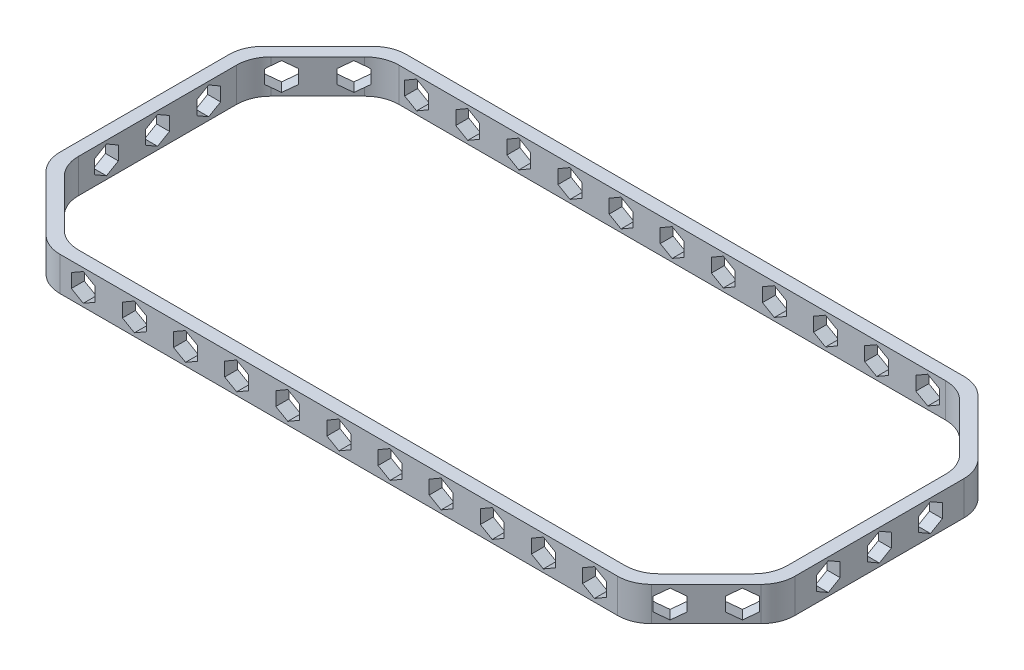
SolidWorks part; units mm, degrees
ref_plane "前视基准面" through (0, 0, 0) normal (0, 0, 1) x (1, 0, 0)
ref_plane "上视基准面" through (0, 0, 0) normal (0, 1, 0) x (1, 0, 0)
ref_plane "右视基准面" through (0, 0, 0) normal (1, 0, 0) x (0, 0, -1)
other "Configuration Table"
sketch "草图1" plane through (0, 0, 0) normal (0, 1, 0) x (1, 0, 0)
  line L0 (85.4765, 52.2785) -> (-86.5723, 52.2785)
  line L1 (-86.5723, 52.2785) -> (-108.5479, 30.3029)
  line L2 (-108.5479, 30.3029) -> (-108.5479, -27.7459)
  line L3 (-108.5479, -27.7459) -> (-86.5723, -49.7215)
  line L4 (-86.5723, -49.7215) -> (85.4765, -49.7215)
  line L5 (85.4765, -49.7215) -> (107.4521, -27.7459)
  line L6 (107.4521, -27.7459) -> (107.4521, 30.3029)
  line L7 (107.4521, 30.3029) -> (85.4765, 52.2785)
  circle A0 centre (-55.5479, 43.7785) radius 1.85
  circle A1 centre (-87.0142, 32.7447) radius 1.85
  circle A2 centre (-100.0479, 1.2785) radius 1.85
  circle A3 centre (-87.0142, -30.1878) radius 1.85
  circle A4 centre (-24.0817, -30.1878) radius 1.85
  circle A5 centre (-24.0817, 32.7447) radius 1.85
  circle A6 centre (-55.5479, -41.2215) radius 1.85
  circle A7 centre (-11.0479, 1.2785) radius 1.85
  circle A8 centre (-55.5479, 1.2785) radius 35
  circle A9 centre (54.4521, 1.2785) radius 35
  circle A10 centre (85.9183, 32.7447) radius 1.85
  circle A11 centre (9.9521, 1.2785) radius 1.85
  circle A12 centre (54.4521, 43.7785) radius 1.85
  circle A13 centre (22.9858, 32.7447) radius 1.85
  circle A14 centre (22.9858, -30.1878) radius 1.85
  circle A15 centre (54.4521, -41.2215) radius 1.85
  circle A16 centre (85.9183, -30.1878) radius 1.85
  circle A17 centre (98.9521, 1.2785) radius 1.85
extrude "凸台-拉伸1" add sketch "草图1" along normal blind 10
sketch "草图2" plane through (0, 10, 0) normal (0, 1, 0) x (1, 0, 0)
  line L0 (103.4521, 28.646) -> (83.8196, 48.2785)
  line L1 (83.8196, 48.2785) -> (-84.9155, 48.2785)
  line L2 (-84.9155, 48.2785) -> (-104.5479, 28.646)
  line L3 (-104.5479, 28.646) -> (-104.5479, -26.0891)
  line L4 (-104.5479, -26.0891) -> (-84.9155, -45.7215)
  line L5 (-84.9155, -45.7215) -> (83.8196, -45.7215)
  line L6 (83.8196, -45.7215) -> (103.4521, -26.0891)
  line L7 (103.4521, -26.0891) -> (103.4521, 28.646)
  line L8 (107.4521, 30.3029) -> (85.4765, 52.2785)
  line L9 (85.4765, 52.2785) -> (-86.5723, 52.2785)
  line L10 (-86.5723, 52.2785) -> (-108.5479, 30.3029)
  line L11 (-108.5479, 30.3029) -> (-108.5479, -27.7459)
  line L12 (-108.5479, -27.7459) -> (-86.5723, -49.7215)
  line L13 (-86.5723, -49.7215) -> (85.4765, -49.7215)
  line L14 (85.4765, -49.7215) -> (107.4521, -27.7459)
  line L15 (107.4521, -27.7459) -> (107.4521, 30.3029)
  line L16 (107.4521, 30.3029) -> (85.4765, 52.2785)
  line L17 (85.4765, 52.2785) -> (-86.5723, 52.2785)
  line L18 (-86.5723, 52.2785) -> (-108.5479, 30.3029)
  line L19 (-108.5479, 30.3029) -> (-108.5479, -27.7459)
  line L20 (-108.5479, -27.7459) -> (-86.5723, -49.7215)
  line L21 (-86.5723, -49.7215) -> (85.4765, -49.7215)
  line L22 (85.4765, -49.7215) -> (107.4521, -27.7459)
  line L23 (107.4521, -27.7459) -> (107.4521, 30.3029)
  circle A1 centre (-55.5479, 43.7785) radius 1.85
  circle A2 centre (-55.5479, 43.7785) radius 1.85
  circle A3 centre (-87.0142, 32.7447) radius 1.85
  circle A4 centre (-87.0142, 32.7447) radius 1.85
  circle A5 centre (-100.0479, 1.2785) radius 1.85
  circle A6 centre (-100.0479, 1.2785) radius 1.85
  circle A7 centre (-87.0142, -30.1878) radius 1.85
  circle A8 centre (-87.0142, -30.1878) radius 1.85
  circle A9 centre (-24.0817, -30.1878) radius 1.85
  circle A10 centre (-24.0817, -30.1878) radius 1.85
  circle A11 centre (-24.0817, 32.7447) radius 1.85
  circle A12 centre (-24.0817, 32.7447) radius 1.85
  circle A13 centre (-55.5479, -41.2215) radius 1.85
  circle A14 centre (-55.5479, -41.2215) radius 1.85
  circle A15 centre (-11.0479, 1.2785) radius 1.85
  circle A16 centre (-11.0479, 1.2785) radius 1.85
  circle A17 centre (-55.5479, 1.2785) radius 35
  circle A18 centre (-55.5479, 1.2785) radius 35
  circle A19 centre (54.4521, 1.2785) radius 35
  circle A20 centre (54.4521, 1.2785) radius 35
  circle A21 centre (85.9183, 32.7447) radius 1.85
  circle A22 centre (85.9183, 32.7447) radius 1.85
  circle A23 centre (9.9521, 1.2785) radius 1.85
  circle A24 centre (9.9521, 1.2785) radius 1.85
  circle A25 centre (54.4521, 43.7785) radius 1.85
  circle A26 centre (54.4521, 43.7785) radius 1.85
  circle A27 centre (22.9858, 32.7447) radius 1.85
  circle A28 centre (22.9858, 32.7447) radius 1.85
  circle A29 centre (22.9858, -30.1878) radius 1.85
  circle A30 centre (22.9858, -30.1878) radius 1.85
  circle A31 centre (54.4521, -41.2215) radius 1.85
  circle A32 centre (54.4521, -41.2215) radius 1.85
  circle A33 centre (85.9183, -30.1878) radius 1.85
  circle A34 centre (85.9183, -30.1878) radius 1.85
  circle A35 centre (98.9521, 1.2785) radius 1.85
  circle A36 centre (98.9521, 1.2785) radius 1.85
  circle M29 centre (85.9183, -30.1878) radius 1.85
  circle M30 centre (22.9858, -30.1878) radius 1.85
  circle M31 centre (54.4521, 43.7785) radius 1.85
  circle M32 centre (85.9183, 32.7447) radius 1.85
  circle M33 centre (-55.5479, 1.2785) radius 35
  circle M34 centre (-55.5479, -41.2215) radius 1.85
  circle M35 centre (-24.0817, -30.1878) radius 1.85
  circle M36 centre (-100.0479, 1.2785) radius 1.85
  circle M37 centre (-55.5479, 43.7785) radius 1.85
  circle M46 centre (-87.0142, 32.7447) radius 1.85
  circle M47 centre (-87.0142, -30.1878) radius 1.85
  circle M48 centre (-24.0817, 32.7447) radius 1.85
  circle M49 centre (-11.0479, 1.2785) radius 1.85
  circle M50 centre (54.4521, 1.2785) radius 35
  circle M51 centre (9.9521, 1.2785) radius 1.85
  circle M52 centre (22.9858, 32.7447) radius 1.85
  circle M53 centre (54.4521, -41.2215) radius 1.85
  circle M54 centre (98.9521, 1.2785) radius 1.85
  dimension "D20" = 4
  dimension "D1" = 0
  dimension "D2" = 0
  dimension "D3" = 0
  dimension "D4" = 0
  dimension "D5" = 0
  dimension "D6" = 0
  dimension "D7" = 0
  dimension "D8" = 0
  dimension "D9" = 0
  dimension "D10" = 0
  dimension "D11" = 0
  dimension "D12" = 0
  dimension "D13" = 0
  dimension "D14" = 0
  dimension "D15" = 0
  dimension "D16" = 0
  dimension "D17" = 0
  dimension "D18" = 0
  dimension "D19" = 0
extrude "切除-拉伸1" cut sketch "草图2" against normal through all contours L6 L7 L0 L1 L2 L3 L4 L5 M29 M31 M33 M35 M37 M46 M48 M50 M52 M54 M53 M51 M49 M47 M36 M34 M32 M30 region at (-0.5479, 10, -1.2785)
sketch "草图3" plane through (0, 10, 0) normal (0, 1, 0) x (1, 0, 0)
  line L0 (107.2521, 30.22) -> (85.3936, 52.0785)
  line L1 (85.3936, 52.0785) -> (-86.4895, 52.0785)
  line L2 (-86.4895, 52.0785) -> (-108.3479, 30.22)
  line L3 (-108.3479, 30.22) -> (-108.3479, -27.6631)
  line L4 (-108.3479, -27.6631) -> (-86.4895, -49.5215)
  line L5 (-86.4895, -49.5215) -> (85.3936, -49.5215)
  line L6 (85.3936, -49.5215) -> (107.2521, -27.6631)
  line L7 (107.2521, -27.6631) -> (107.2521, 30.22)
  line L8 (107.4521, 30.3029) -> (85.4765, 52.2785)
  line L9 (85.4765, 52.2785) -> (-86.5723, 52.2785)
  line L10 (-86.5723, 52.2785) -> (-108.5479, 30.3029)
  line L11 (-108.5479, 30.3029) -> (-108.5479, -27.7459)
  line L12 (-108.5479, -27.7459) -> (-86.5723, -49.7215)
  line L13 (-86.5723, -49.7215) -> (85.4765, -49.7215)
  line L14 (85.4765, -49.7215) -> (107.4521, -27.7459)
  line L15 (107.4521, -27.7459) -> (107.4521, 30.3029)
  line L16 (107.4521, 30.3029) -> (85.4765, 52.2785)
  line L17 (85.4765, 52.2785) -> (-86.5723, 52.2785)
  line L18 (-86.5723, 52.2785) -> (-108.5479, 30.3029)
  line L19 (-108.5479, 30.3029) -> (-108.5479, -27.7459)
  line L20 (-108.5479, -27.7459) -> (-86.5723, -49.7215)
  line L21 (-86.5723, -49.7215) -> (85.4765, -49.7215)
  line L22 (85.4765, -49.7215) -> (107.4521, -27.7459)
  line L23 (107.4521, -27.7459) -> (107.4521, 30.3029)
  dimension "D1" = 0
  dimension "D2" = 0.2
extrude "切除-拉伸2" cut sketch "草图3" against normal through all
sketch "草图4" plane through (0, 0, -52.0785) normal (0, 0, -1) x (-1, 0, 0)
  line L0 (-85.3936, 5) -> (86.4895, 5) construction
  line L1 (0.5479, 10) -> (0.5479, 0) construction
  line L2 (-59.4521, 9.0415) -> (-62.9521, 7.0207)
  line L3 (-74.4521, 9.0415) -> (-77.9521, 7.0207)
  line L4 (86.4895, 10) -> (-85.3936, 10)
  line L5 (-85.3936, 10) -> (-85.3936, 0)
  line L6 (-85.3936, 0) -> (86.4895, 0)
  line L7 (86.4895, 0) -> (86.4895, 10)
  line L8 (86.4895, 10) -> (-85.3936, 10) construction
  line L9 (-85.3936, 10) -> (-85.3936, 0) construction
  line L10 (-85.3936, 0) -> (86.4895, 0) construction
  line L11 (86.4895, 0) -> (86.4895, 10) construction
  line L12 (-77.9521, 7.0207) -> (-77.9521, 2.9793)
  line L13 (-77.9521, 2.9793) -> (-74.4521, 0.9585)
  line L14 (-74.4521, 0.9585) -> (-70.9521, 2.9793)
  line L15 (-70.9521, 2.9793) -> (-70.9521, 7.0207)
  line L16 (-70.9521, 7.0207) -> (-74.4521, 9.0415)
  line L17 (-62.9521, 7.0207) -> (-62.9521, 2.9793)
  line L18 (-62.9521, 2.9793) -> (-59.4521, 0.9585)
  line L19 (-59.4521, 0.9585) -> (-55.9521, 2.9793)
  line L20 (-55.9521, 2.9793) -> (-55.9521, 7.0207)
  line L21 (-55.9521, 7.0207) -> (-59.4521, 9.0415)
  line L22 (-44.4521, 9.0415) -> (-47.9521, 7.0207)
  line L23 (-47.9521, 7.0207) -> (-47.9521, 2.9793)
  line L24 (-47.9521, 2.9793) -> (-44.4521, 0.9585)
  line L25 (-44.4521, 0.9585) -> (-40.9521, 2.9793)
  line L26 (-40.9521, 2.9793) -> (-40.9521, 7.0207)
  line L27 (-40.9521, 7.0207) -> (-44.4521, 9.0415)
  line L28 (-29.4521, 9.0415) -> (-32.9521, 7.0207)
  line L29 (-32.9521, 7.0207) -> (-32.9521, 2.9793)
  line L30 (-32.9521, 2.9793) -> (-29.4521, 0.9585)
  line L31 (-29.4521, 0.9585) -> (-25.9521, 2.9793)
  line L32 (-25.9521, 2.9793) -> (-25.9521, 7.0207)
  line L33 (-25.9521, 7.0207) -> (-29.4521, 9.0415)
  line L34 (-14.4521, 9.0415) -> (-17.9521, 7.0207)
  line L35 (-17.9521, 7.0207) -> (-17.9521, 2.9793)
  line L36 (-17.9521, 2.9793) -> (-14.4521, 0.9585)
  line L37 (-14.4521, 0.9585) -> (-10.9521, 2.9793)
  line L38 (-10.9521, 2.9793) -> (-10.9521, 7.0207)
  line L39 (-10.9521, 7.0207) -> (-14.4521, 9.0415)
  line L40 (0.5479, 9.0415) -> (-2.9521, 7.0207)
  line L41 (-2.9521, 7.0207) -> (-2.9521, 2.9793)
  line L42 (-2.9521, 2.9793) -> (0.5479, 0.9585)
  line L43 (0.5479, 0.9585) -> (4.0479, 2.9793)
  line L44 (4.0479, 2.9793) -> (4.0479, 7.0207)
  line L45 (4.0479, 7.0207) -> (0.5479, 9.0415)
  line L46 (15.5479, 9.0415) -> (12.0479, 7.0207)
  line L47 (12.0479, 7.0207) -> (12.0479, 2.9793)
  line L48 (12.0479, 2.9793) -> (15.5479, 0.9585)
  line L49 (15.5479, 0.9585) -> (19.0479, 2.9793)
  line L50 (19.0479, 2.9793) -> (19.0479, 7.0207)
  line L51 (19.0479, 7.0207) -> (15.5479, 9.0415)
  line L52 (30.5479, 9.0415) -> (27.0479, 7.0207)
  line L53 (27.0479, 7.0207) -> (27.0479, 2.9793)
  line L54 (27.0479, 2.9793) -> (30.5479, 0.9585)
  line L55 (30.5479, 0.9585) -> (34.0479, 2.9793)
  line L56 (34.0479, 2.9793) -> (34.0479, 7.0207)
  line L57 (34.0479, 7.0207) -> (30.5479, 9.0415)
  line L58 (45.5479, 9.0415) -> (42.0479, 7.0207)
  line L59 (42.0479, 7.0207) -> (42.0479, 2.9793)
  line L60 (42.0479, 2.9793) -> (45.5479, 0.9585)
  line L61 (45.5479, 0.9585) -> (49.0479, 2.9793)
  line L62 (49.0479, 2.9793) -> (49.0479, 7.0207)
  line L63 (49.0479, 7.0207) -> (45.5479, 9.0415)
  line L64 (60.5479, 9.0415) -> (57.0479, 7.0207)
  line L65 (57.0479, 7.0207) -> (57.0479, 2.9793)
  line L66 (57.0479, 2.9793) -> (60.5479, 0.9585)
  line L67 (60.5479, 0.9585) -> (64.0479, 2.9793)
  line L68 (64.0479, 2.9793) -> (64.0479, 7.0207)
  line L69 (64.0479, 7.0207) -> (60.5479, 9.0415)
  line L70 (75.5479, 9.0415) -> (72.0479, 7.0207)
  line L71 (72.0479, 7.0207) -> (72.0479, 2.9793)
  line L72 (72.0479, 2.9793) -> (75.5479, 0.9585)
  line L73 (75.5479, 0.9585) -> (79.0479, 2.9793)
  line L74 (79.0479, 2.9793) -> (79.0479, 7.0207)
  line L75 (79.0479, 7.0207) -> (75.5479, 9.0415)
  circle A0 centre (-74.4521, 5) radius 3.5 construction
  point P9 (0.5479, 9.0415)
  point P17 (-73.2649, 1.8934)
  point P78 (0.5479, 0.9585)
  dimension "D2" = 7
  dimension "D4" = 15
  dimension "D1" = 0
  dimension "D3" = 11
extrude "切除-拉伸3" cut sketch "草图4" against normal through all
sketch "草图5" plane through (-108.3479, 0, 0) normal (-1, 0, 0) x (0, 0, 1)
  line L0 (-30.22, 5) -> (27.6631, 5) construction
  line L1 (27.6631, 0) -> (27.6631, 10) construction
  line L2 (-1.2785, 10) -> (-1.2785, 0) construction
  line L3 (-1.2785, 9.0415) -> (-4.7785, 7.0207)
  line L4 (27.6631, 10) -> (-30.22, 10)
  line L5 (-30.22, 10) -> (-30.22, 0)
  line L6 (-30.22, 0) -> (27.6631, 0)
  line L7 (27.6631, 0) -> (27.6631, 10)
  line L8 (27.6631, 10) -> (-30.22, 10) construction
  line L9 (-30.22, 10) -> (-30.22, 0) construction
  line L10 (-30.22, 0) -> (27.6631, 0) construction
  line L11 (27.6631, 0) -> (27.6631, 10) construction
  line L12 (-16.2785, 9.0415) -> (-19.7785, 7.0207)
  line L13 (-19.7785, 7.0207) -> (-19.7785, 2.9793)
  line L14 (-19.7785, 2.9793) -> (-16.2785, 0.9585)
  line L15 (-16.2785, 0.9585) -> (-12.7785, 2.9793)
  line L16 (-12.7785, 2.9793) -> (-12.7785, 7.0207)
  line L17 (-12.7785, 7.0207) -> (-16.2785, 9.0415)
  line L18 (-4.7785, 7.0207) -> (-4.7785, 2.9793)
  line L19 (-4.7785, 2.9793) -> (-1.2785, 0.9585)
  line L20 (-1.2785, 0.9585) -> (2.2215, 2.9793)
  line L21 (2.2215, 2.9793) -> (2.2215, 7.0207)
  line L22 (2.2215, 7.0207) -> (-1.2785, 9.0415)
  line L23 (13.7215, 9.0415) -> (10.2215, 7.0207)
  line L24 (10.2215, 7.0207) -> (10.2215, 2.9793)
  line L25 (10.2215, 2.9793) -> (13.7215, 0.9585)
  line L26 (13.7215, 0.9585) -> (17.2215, 2.9793)
  line L27 (17.2215, 2.9793) -> (17.2215, 7.0207)
  line L28 (17.2215, 7.0207) -> (13.7215, 9.0415)
  circle A0 centre (-16.2785, 5) radius 3.5 construction
  point P11 (0, 0)
  point P19 (0, 0)
  point P32 (-1.2785, 8.9285)
  point P33 (-1.2785, 0.9585)
  dimension "D2" = 7
  dimension "D4" = 15
  dimension "D1" = 0
  dimension "D3" = 3
extrude "切除-拉伸4" cut sketch "草图5" against normal through all
sketch "草图6" plane through (-69.284, 0, -69.284) normal (-0.7071, 0, -0.7071) x (-0.7071, 0, 0.7071)
  line L0 (24.3322, 5) -> (55.2448, 5) construction
  line L1 (47.2885, 9.0415) -> (43.7885, 7.0207)
  line L2 (32.2885, 9.0415) -> (28.7885, 7.0207)
  line L3 (28.7885, 7.0207) -> (28.7885, 2.9793)
  line L4 (55.2448, 10) -> (24.3322, 10)
  line L5 (24.3322, 10) -> (24.3322, 0)
  line L6 (24.3322, 0) -> (55.2448, 0)
  line L7 (55.2448, 0) -> (55.2448, 10)
  line L8 (55.2448, 10) -> (24.3322, 10) construction
  line L9 (24.3322, 10) -> (24.3322, 0)
  line L10 (24.3322, 0) -> (55.2448, 0) construction
  line L11 (55.2448, 0) -> (55.2448, 10)
  line L12 (28.7885, 2.9793) -> (32.2885, 0.9585)
  line L13 (32.2885, 0.9585) -> (35.7885, 2.9793)
  line L14 (35.7885, 2.9793) -> (35.7885, 7.0207)
  line L15 (35.7885, 7.0207) -> (32.2885, 9.0415)
  line L16 (43.7885, 7.0207) -> (43.7885, 2.9793)
  line L17 (43.7885, 2.9793) -> (47.2885, 0.9585)
  line L18 (47.2885, 0.9585) -> (50.7885, 2.9793)
  line L19 (50.7885, 2.9793) -> (50.7885, 7.0207)
  line L20 (50.7885, 7.0207) -> (47.2885, 9.0415)
  line L21 (39.7885, 10) -> (39.7885, 0) construction
  circle A0 centre (32.2885, 5) radius 3.5 construction
  dimension "D2" = 7
  dimension "D4" = 15
  dimension "D5" = 7.5
  dimension "D6" = 7.5
  dimension "D1" = 0
  dimension "D3" = 2
extrude "切除-拉伸5" cut sketch "草图6" against normal blind 5 contours L14 L15 L2 L3 L12 L13 | L19 L20 L1 L16 L17 L18 region at (-102.722, 5, -35.8459) region at (-92.1154, 5, -46.4525)
sketch "草图7" plane through (-68.0055, 0, 68.0055) normal (-0.7071, 0, 0.7071) x (0.7071, 0, 0.7071)
  line L0 (-57.0528, 5) -> (-26.1403, 5) construction
  line L1 (-41.5965, 10) -> (-41.5965, 0) construction
  line L2 (-49.0965, 9.0415) -> (-52.5965, 7.0207)
  line L3 (-52.5965, 7.0207) -> (-52.5965, 2.9793)
  line L4 (-26.1403, 10) -> (-57.0528, 10)
  line L5 (-57.0528, 10) -> (-57.0528, 0)
  line L6 (-57.0528, 0) -> (-26.1403, 0)
  line L7 (-26.1403, 0) -> (-26.1403, 10)
  line L8 (-26.1403, 10) -> (-57.0528, 10) construction
  line L9 (-57.0528, 10) -> (-57.0528, 0) construction
  line L10 (-57.0528, 0) -> (-26.1403, 0) construction
  line L11 (-26.1403, 0) -> (-26.1403, 10) construction
  line L12 (-52.5965, 2.9793) -> (-49.0965, 0.9585)
  line L13 (-49.0965, 0.9585) -> (-45.5965, 2.9793)
  line L14 (-45.5965, 2.9793) -> (-45.5965, 7.0207)
  line L15 (-45.5965, 7.0207) -> (-49.0965, 9.0415)
  line L16 (-34.0965, 9.0415) -> (-37.5965, 7.0207)
  line L17 (-37.5965, 7.0207) -> (-37.5965, 2.9793)
  line L18 (-37.5965, 2.9793) -> (-34.0965, 0.9585)
  line L19 (-34.0965, 0.9585) -> (-30.5965, 2.9793)
  line L20 (-30.5965, 2.9793) -> (-30.5965, 7.0207)
  line L21 (-30.5965, 7.0207) -> (-34.0965, 9.0415)
  circle A0 centre (-49.0965, 5) radius 3.5 construction
  point P16 (0, 0)
  dimension "D2" = 7
  dimension "D4" = 7.5
  dimension "D5" = 7.5
  dimension "D6" = 15
  dimension "D1" = 0
  dimension "D3" = 2
extrude "切除-拉伸6" cut sketch "草图7" against normal blind 5
sketch "草图8" plane through (68.7361, 0, -68.7361) normal (0.7071, 0, -0.7071) x (-0.7071, 0, -0.7071)
  line L0 (-39.0136, 10) -> (-39.0136, 0) construction
  line L1 (-54.4699, 5) -> (-23.5574, 5) construction
  line L2 (-35.0136, 7.0207) -> (-31.5136, 9.0415)
  line L3 (-46.5136, 9.0415) -> (-50.0136, 7.0207)
  line L4 (-23.5574, 10) -> (-54.4699, 10)
  line L5 (-54.4699, 10) -> (-54.4699, 0)
  line L6 (-54.4699, 0) -> (-23.5574, 0)
  line L7 (-23.5574, 0) -> (-23.5574, 10)
  line L8 (-23.5574, 10) -> (-54.4699, 10) construction
  line L9 (-54.4699, 10) -> (-54.4699, 0) construction
  line L10 (-54.4699, 0) -> (-23.5574, 0) construction
  line L11 (-23.5574, 0) -> (-23.5574, 10) construction
  line L12 (-50.0136, 7.0207) -> (-50.0136, 2.9793)
  line L13 (-50.0136, 2.9793) -> (-46.5136, 0.9585)
  line L14 (-46.5136, 0.9585) -> (-43.0136, 2.9793)
  line L15 (-43.0136, 2.9793) -> (-43.0136, 7.0207)
  line L16 (-43.0136, 7.0207) -> (-46.5136, 9.0415)
  line L17 (-35.0136, 2.9793) -> (-35.0136, 7.0207)
  line L18 (-31.5136, 0.9585) -> (-35.0136, 2.9793)
  line L19 (-28.0136, 2.9793) -> (-31.5136, 0.9585)
  line L20 (-28.0136, 7.0207) -> (-28.0136, 2.9793)
  line L21 (-31.5136, 9.0415) -> (-28.0136, 7.0207)
  circle A0 centre (-46.5136, 5) radius 3.5 construction
  dimension "D2" = 7
  dimension "D3" = 7.5
  dimension "D4" = 7.5
  dimension "D1" = 0
extrude "切除-拉伸7" cut sketch "草图8" against normal blind 5
sketch "草图9" plane through (67.4576, 0, 67.4576) normal (0.7071, 0, 0.7071) x (0.7071, 0, -0.7071)
  line L0 (25.3654, 5) -> (56.2779, 5) construction
  line L1 (56.2779, 0) -> (56.2779, 10) construction
  line L2 (40.8217, 10) -> (40.8217, 0) construction
  line L3 (44.8217, 7.0207) -> (48.3217, 9.0415)
  line L4 (56.2779, 10) -> (25.3654, 10)
  line L5 (25.3654, 10) -> (25.3654, 0)
  line L6 (25.3654, 0) -> (56.2779, 0)
  line L7 (56.2779, 0) -> (56.2779, 10)
  line L8 (56.2779, 10) -> (25.3654, 10) construction
  line L9 (25.3654, 10) -> (25.3654, 0) construction
  line L10 (25.3654, 0) -> (56.2779, 0) construction
  line L11 (56.2779, 0) -> (56.2779, 10) construction
  line L12 (33.3217, 9.0415) -> (29.8217, 7.0207)
  line L13 (29.8217, 7.0207) -> (29.8217, 2.9793)
  line L14 (29.8217, 2.9793) -> (33.3217, 0.9585)
  line L15 (33.3217, 0.9585) -> (36.8217, 2.9793)
  line L16 (36.8217, 2.9793) -> (36.8217, 7.0207)
  line L17 (36.8217, 7.0207) -> (33.3217, 9.0415)
  line L18 (44.8217, 2.9793) -> (44.8217, 7.0207)
  line L19 (48.3217, 0.9585) -> (44.8217, 2.9793)
  line L20 (51.8217, 2.9793) -> (48.3217, 0.9585)
  line L21 (51.8217, 7.0207) -> (51.8217, 2.9793)
  line L22 (48.3217, 9.0415) -> (51.8217, 7.0207)
  circle A0 centre (33.3217, 5) radius 3.5 construction
  dimension "D2" = 7.5
  dimension "D3" = 7.5
  dimension "D4" = 7
  dimension "D1" = 0
extrude "切除-拉伸8" cut sketch "草图9" against normal blind 5
fillet "圆角1" radius 10 16 edges at (83.8196, 5, 45.7215) (103.4521, 5, 26.0891) (103.4521, 5, -28.646) (83.8196, 5, -48.2785) (-84.9155, 5, -48.2785) (-104.5479, 5, -28.646) (-104.5479, 5, 26.0891) (-84.9155, 5, 45.7215) (85.3936, 5, 49.5215) (107.2521, 5, 27.6631) (107.2521, 5, -30.22) (85.3936, 5, -52.0785) (-86.4895, 5, -52.0785) (-108.3479, 5, -30.22) (-86.4895, 5, 49.5215) (-108.3479, 5, 27.6631)
